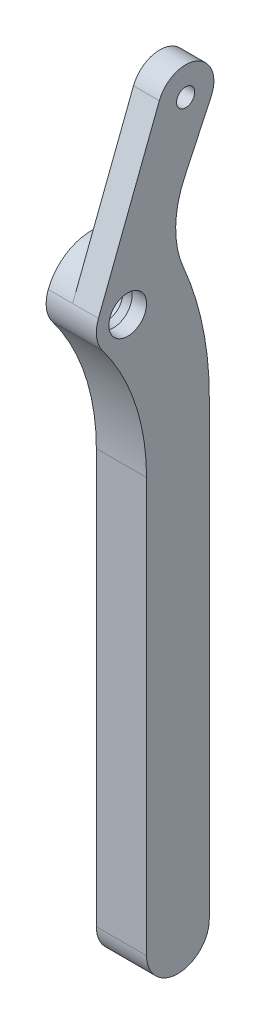
SolidWorks part; units mm, degrees
ref_plane "Front Plane" through (0, 0, 0) normal (0, 0, 1) x (1, 0, 0)
ref_plane "Top Plane" through (0, 0, 0) normal (0, 1, 0) x (1, 0, 0)
ref_plane "Right Plane" through (0, 0, 0) normal (1, 0, 0) x (0, 0, -1)
sketch "Sketch1" plane through (0, 0, 0) normal (1, 0, 0) x (0, 0, -1)
  line L0 (13, -90) -> (13, -17.7993)
  line L1 (5.0352, 26.9888) -> (-4.666, 1.7968)
  line L2 (3, -90) -> (3, -24)
  line L3 (0, 0) -> (9.2345, 25.3717) construction
  line L4 (0, 0) -> (0, 25.3717) construction
  line L5 (0, 25.3717) -> (9.2345, 25.3717) construction
  line L6 (9.0631, 14.4072) -> (13.3088, 23.4611)
  circle A0 centre (0, 0) radius 5
  circle A1 centre (9.2345, 25.3717) radius 4.5
  circle A2 centre (8, -90) radius 5
  arc A3 (3, -24) -> (-4, -3) centre (-32, -24) ccw
  arc A4 (13, -17.7993) -> (8.88, 2.076) centre (-37, -17.7993) ccw
  arc A5 (8.88, 2.076) -> (9.0631, 14.4072) centre (22.644, 8.0386) cw
  circle A6 centre (9.2345, 25.3717) radius 1.45
  circle A7 centre (0, 0) radius 2.5
  arc A8 (8.88, 2.076) -> (-4.666, 1.7968) centre (2.1641, -0.8334) ccw
  dimension "D2" = 9
  dimension "D3" = 10
  dimension "D4" = 10
  dimension "D7" = 15
  dimension "D9" = 50
  dimension "D10" = 35
  dimension "D12" = 2.9
  dimension "D13" = 5
  dimension "D1" = 20
  dimension "D5" = 3
  dimension "D6" = 90
  dimension "D8" = 27
  dimension "D11" = 10
extrude "Boss-Extrude1" add sketch "Sketch1" along normal mid plane 8 contours A1 A6 | A5 L6 A1 L1 A0 | A0 A7 | L0 A4 A0 A3 L2 A2 | A2 region at (0, -41.085, -7.5555) region at (0, -90, -8) region at (0, 13.7046, -4.4718) region at (0, 4.7767, -0.888) region at (0, 21.3494, -7.5195)
sketch "Sketch2" plane through (4, 0, 0) normal (1, 0, 0) x (0, 0, -1)
  circle A0 centre (0, 0) radius 3
  dimension "D1" = 6
extrude "Cut-Extrude1" cut sketch "Sketch2" against normal blind 3.3
extrude "Cut-Extrude2" cut sketch "Sketch1<5>" against normal through all from offset 0.12 contours A8 A5 L6 A1 L1 | A1 A6 region at (0, 13.7046, -4.4718) region at (0, 21.3494, -7.5195) offset against normal yes
sketch "Sketch1<5>" plane through (0, 0, 0) normal (1, 0, 0) x (0, 0, -1) same geometry as "Sketch1"
extrude "Cut-Extrude3" cut sketch "Sketch2<2>" along normal blind 2.3 from surface starting at face at (-4, 0, -2.5)
sketch "Sketch2<2>" plane through (4, 0, 0) normal (1, 0, 0) x (0, 0, -1) same geometry as "Sketch2"
chamfer "Chamfer1" distance 1 distance2 0.5 1 edges at (0.7, 0, -3) first distance on face at (0.7, 0, -3)
move or copy body "Body-Move/Copy1" [suppressed] bodies to move or copy 106
